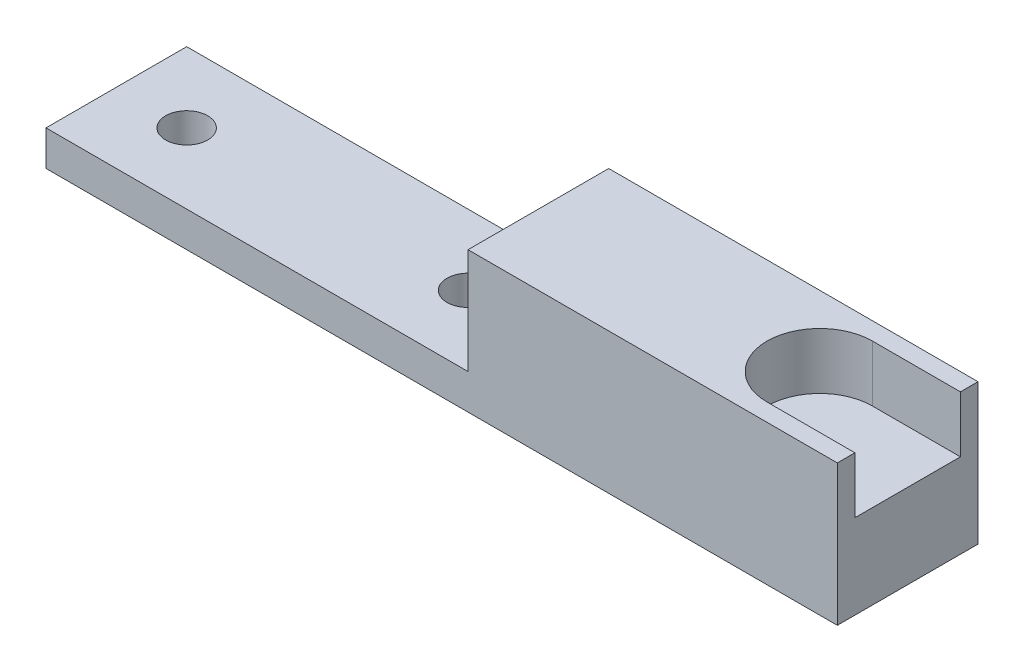
SolidWorks part; units mm, degrees
material "6061 Alloy"
ref_plane "Front Plane" through (0, 0, 0) normal (0, 0, 1) x (1, 0, 0)
ref_plane "Top Plane" through (0, 0, 0) normal (0, 1, 0) x (1, 0, 0)
ref_plane "Right Plane" through (0, 0, 0) normal (1, 0, 0) x (0, 0, -1)
sketch "Sketch1" plane through (0, 0, 0) normal (0, 1, 0) x (1, 0, 0)
  line L1 (-35.7187, -6.35) -> (35.7188, -6.35)
  line L2 (-35.7187, -6.35) -> (-35.7187, 6.35)
  line L3 (-35.7187, 6.35) -> (35.7188, 6.35)
  line L4 (35.7188, -6.35) -> (35.7188, 6.35)
  line L5 (-35.7187, -6.35) -> (35.7188, 6.35) construction
  line L6 (-35.7187, 6.35) -> (35.7188, -6.35) construction
  point P0 (0, 0)
  dimension "D1" = 12.7
  dimension "D2" = 71.4375
extrude "Boss-Extrude1" add sketch "Sketch1" along normal blind 12.7
hole_wizard "#6 Clearance Hole2" positions "Sketch4" profile "Sketch5" hole size "#6" standard "ANSI Inch" end condition through all
sketch "Sketch4" plane through (0, 0, 0) normal (0, -1, 0) x (-1, 0, 0)
  line L0 (35.7187, 6.35) -> (35.7187, -6.35) construction
  line L1 (-35.7188, 6.35) -> (35.7187, 6.35) construction
  point P0 (29.3687, 0)
  point P2 (3.9687, 0)
  dimension "D1" = 6.35
  dimension "D2" = 25.4
  dimension "D3" = 6.35
  dimension "D4" = 6.35
sketch "Sketch5" plane through (-29.3687, 0, 0) normal (1, 0, 0) x (0, 0, -1)
  line L0 (0, 0) -> (0, 12.7)
  line L1 (0, 12.7) -> (1.8986, 12.7)
  line L2 (1.8986, 12.7) -> (1.8986, 0)
  line L5 (1.8986, 0) -> (0, 0)
  line L11 (0, -6.35) -> (0, 107.95) construction
  dimension "Thru Hole Dia." = 3.7973
  dimension "Thru Hole Depth" = 12.7
sketch "Sketch6" plane through (0, 0, 6.35) normal (0, 0, 1) x (1, 0, 0)
  line L1 (-35.7187, 12.7) -> (2.3813, 12.7)
  line L2 (-35.7187, 12.7) -> (-35.7187, 3.175)
  line L3 (-35.7187, 3.175) -> (2.3813, 3.175)
  line L4 (2.3813, 12.7) -> (2.3813, 3.175)
  dimension "D1" = 38.1
  dimension "D2" = 9.525
extrude "Cut-Extrude1" cut sketch "Sketch6" against normal through all
sketch "Sketch8" plane through (0, 12.7, 0) normal (0, 1, 0) x (1, 0, 0)
  line L0 (35.7188, -6.35) -> (35.7188, 6.35) construction
  line L1 (23.0188, -4.7625) -> (35.7188, -4.7625)
  line L2 (23.0188, -4.7625) -> (23.0188, 4.7625)
  line L3 (23.0188, 4.7625) -> (35.7188, 4.7625)
  line L4 (35.7188, -4.7625) -> (35.7188, 4.7625)
  line L5 (23.0188, -4.7625) -> (35.7188, 4.7625) construction
  line L6 (23.0188, 4.7625) -> (35.7188, -4.7625) construction
  circle A1 centre (27.7813, 0) radius 4.7625
  point P0 (29.3688, 0)
  point P7 (0, 0)
  line M6 (35.7188, -6.35) -> (35.7188, 6.35)
  dimension "D1" = 12.7
  dimension "D2" = 9.525
  dimension "D3" = 0
extrude "Cut-Extrude2" cut sketch "Sketch8" against normal blind 5.08 contours A1 | A1 L1 L3 M6 region at (33.4856, 12.7, 0) region at (27.7813, 12.7, 0)
